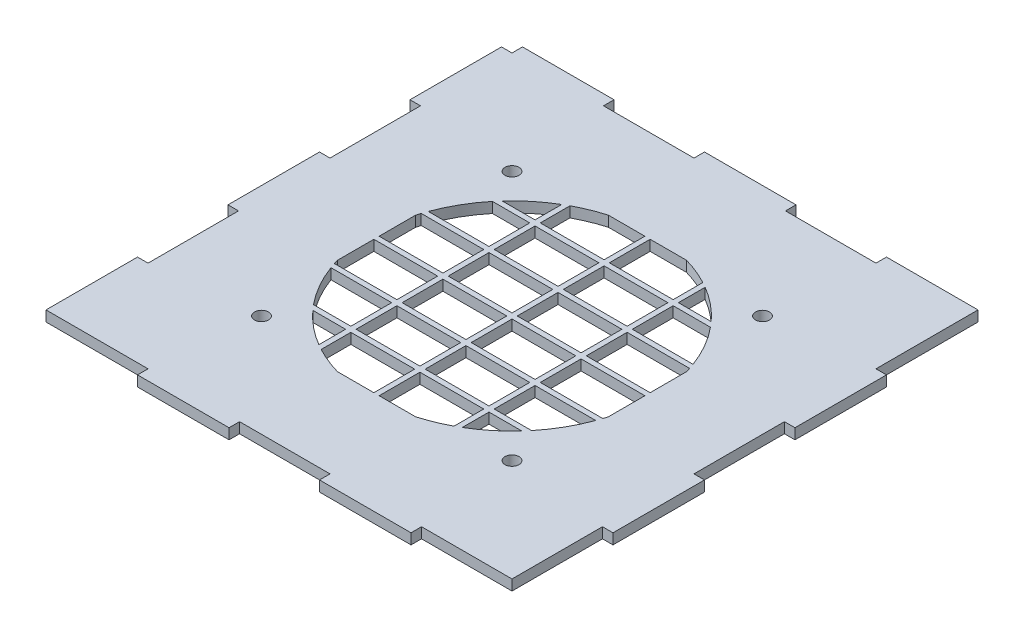
SolidWorks part; units mm, degrees
ref_plane "Front Plane" through (0, 0, 0) normal (0, 0, 1) x (1, 0, 0)
ref_plane "Top Plane" through (0, 0, 0) normal (0, 1, 0) x (1, 0, 0)
ref_plane "Right Plane" through (0, 0, 0) normal (1, 0, 0) x (0, 0, -1)
sketch "Sketch1" plane through (0, 0, 0) normal (0, 1, 0) x (1, 0, 0)
  line L0 (0, 38.675) -> (0, 65) construction
  line L1 (-38.675, 0) -> (-65, 0) construction
  line L2 (0, -38.675) -> (0, -65) construction
  line L7 (11.1493, -38.675) -> (-11.1493, -38.675)
  line L8 (38.675, -11.1493) -> (38.675, 11.1493)
  line L21 (11.1493, 38.675) -> (-11.1493, 38.675)
  line L45 (-38.675, -11.1493) -> (-38.675, 11.1493)
  line L46 (38.675, -38.675) -> (-38.675, 38.675) construction
  line L99 (38.675, 38.675) -> (-38.675, -38.675) construction
  line L116 (65, 38.88) -> (68, 38.88)
  line L117 (-65, -38.88) -> (-65, -13.06)
  line L118 (68, 38.88) -> (68, 12.76)
  line L119 (68, 12.76) -> (65, 12.76)
  line L120 (38.675, 0) -> (65, 0) construction
  line L121 (-13.06, 65) -> (-38.88, 65)
  line L122 (-38.88, 65) -> (-38.88, 68)
  line L123 (-13.06, 65) -> (-13.06, 68)
  line L124 (-13.06, 68) -> (13.06, 68)
  line L125 (13.06, 65) -> (13.06, 68)
  line L126 (38.88, 65) -> (38.88, 68)
  line L127 (38.88, 68) -> (65, 68)
  line L128 (38.88, 65) -> (13.06, 65)
  line L129 (-65, 66.5) -> (-39.18, 66.5) construction
  line L130 (-39.18, 66.5) -> (-38.88, 66.5) construction
  line L131 (-65, 38.88) -> (-68, 38.88)
  line L132 (-65, 13.06) -> (-68, 13.06)
  line L133 (-65, -13.06) -> (-68, -13.06)
  line L134 (-68, 13.06) -> (-68, -13.06)
  line L135 (-65, -38.88) -> (-68, -38.88)
  line L136 (-68, -65) -> (-68, -38.88)
  line L137 (-65, 13.06) -> (-65, 38.88)
  line L138 (-38.88, -65) -> (-64.7, -65)
  line L139 (65, 12.76) -> (65, -13.06)
  line L140 (65, -13.06) -> (68, -13.06)
  line L141 (68, -13.06) -> (68, -39.18)
  line L142 (68, -39.18) -> (65, -39.18)
  line L143 (65, -39.18) -> (65, -65)
  line L144 (65, -65) -> (39.18, -65)
  line L145 (39.18, -65) -> (39.18, -68)
  line L146 (39.18, -68) -> (13.06, -68)
  line L147 (13.06, -68) -> (13.06, -65)
  line L148 (13.06, -65) -> (-12.76, -65)
  line L149 (-12.76, -65) -> (-12.76, -68)
  line L150 (-12.76, -68) -> (-38.88, -68)
  line L151 (-38.88, -68) -> (-38.88, -65)
  line L152 (-64.7, -65) -> (-68, -65)
  line L153 (65, 68) -> (65, 64.7)
  line L154 (65, 64.7) -> (65, 38.88)
  line L155 (-38.88, 68) -> (-65, 68)
  line L156 (-65, 68) -> (-65, 65)
  line L157 (-65, 65) -> (-68, 65)
  line L158 (-68, 65) -> (-68, 38.88)
  arc A9 (-38.675, -11.1493) -> (-11.1493, -38.675) centre (0, 0) ccw
  arc A10 (-11.1493, 38.675) -> (-38.675, 11.1493) centre (0, 0) ccw
  arc A11 (38.675, 11.1493) -> (11.1493, 38.675) centre (0, 0) ccw
  arc A12 (11.1493, -38.675) -> (38.675, -11.1493) centre (0, 0) ccw
  dimension "D3" = 0.3
  dimension "D2" = 80.5
  dimension "D1" = 77.35
  dimension "D4" = 3
  dimension "D5" = 130
extrude "Boss-Extrude1" add sketch "Sketch1" along normal blind 3
sketch "Sketch2" plane through (0, 3, 0) normal (0, 1, 0) x (1, 0, 0)
  line L1 (-65, 40.175) -> (65, 40.175)
  line L2 (-65, 40.175) -> (-65, 38.675)
  line L3 (-65, 38.675) -> (65, 38.675)
  line L4 (65, 40.175) -> (65, 38.675)
  line L5 (-11.1493, -38.675) -> (11.1493, -38.675) construction
  line L7 (-65, 27.0333) -> (-65, 25.5333)
  line L8 (-65, 27.0333) -> (65, 27.0333)
  line L9 (65, 27.0333) -> (65, 25.5333)
  line L10 (-65, 25.5333) -> (65, 25.5333)
  line L11 (-65, 13.8917) -> (-65, 12.3917)
  line L12 (-65, 13.8917) -> (65, 13.8917)
  line L13 (65, 13.8917) -> (65, 12.3917)
  line L14 (-65, 12.3917) -> (65, 12.3917)
  line L15 (-65, 0.75) -> (-65, -0.75)
  line L16 (-65, 0.75) -> (65, 0.75)
  line L17 (65, 0.75) -> (65, -0.75)
  line L18 (-65, -0.75) -> (65, -0.75)
  line L19 (-65, -12.3917) -> (-65, -13.8917)
  line L20 (-65, -12.3917) -> (65, -12.3917)
  line L21 (65, -12.3917) -> (65, -13.8917)
  line L22 (-65, -13.8917) -> (65, -13.8917)
  line L23 (-65, -25.5333) -> (-65, -27.0333)
  line L24 (-65, -25.5333) -> (65, -25.5333)
  line L25 (65, -25.5333) -> (65, -27.0333)
  line L26 (-65, -27.0333) -> (65, -27.0333)
  line L27 (-65, -38.675) -> (-65, -40.175)
  line L28 (-65, -38.675) -> (65, -38.675)
  line L29 (65, -38.675) -> (65, -40.175)
  line L30 (-65, -40.175) -> (65, -40.175)
  line L57 (11.1493, 38.675) -> (-11.1493, 38.675) construction
  line L60 (-65, 38.88) -> (-65, 13.06) construction
  line L61 (65, 38.88) -> (65, 68) construction
  dimension "D1" = 1.5
  dimension "D2" = 7
extrude "Boss-Extrude2" add sketch "Sketch2" against normal through all
sketch "Sketch3" plane through (0, 3, 0) normal (0, 1, 0) x (1, 0, 0)
  line L1 (38.675, 0.75) -> (38.675, 11.1493) construction
  line L2 (-38.675, -38.675) -> (-40.175, -38.675)
  line L3 (-38.675, -38.675) -> (-38.675, 38.675)
  line L4 (-38.675, 38.675) -> (-40.175, 38.675)
  line L5 (-40.175, -38.675) -> (-40.175, 38.675)
  line L6 (-38.675, -0.75) -> (-38.675, -11.1493) construction
  line L8 (-18.9625, -38.675) -> (-18.9625, 38.675)
  line L9 (-18.9625, -38.675) -> (-20.4625, -38.675)
  line L10 (-20.4625, -38.675) -> (-20.4625, 38.675)
  line L11 (-18.9625, 38.675) -> (-20.4625, 38.675)
  line L12 (0.75, -38.675) -> (0.75, 38.675)
  line L13 (0.75, -38.675) -> (-0.75, -38.675)
  line L14 (-0.75, -38.675) -> (-0.75, 38.675)
  line L15 (0.75, 38.675) -> (-0.75, 38.675)
  line L16 (20.4625, -38.675) -> (20.4625, 38.675)
  line L17 (20.4625, -38.675) -> (18.9625, -38.675)
  line L18 (18.9625, -38.675) -> (18.9625, 38.675)
  line L19 (20.4625, 38.675) -> (18.9625, 38.675)
  line L20 (40.175, -38.675) -> (40.175, 38.675)
  line L21 (40.175, -38.675) -> (38.675, -38.675)
  line L22 (38.675, -38.675) -> (38.675, 38.675)
  line L23 (40.175, 38.675) -> (38.675, 38.675)
  line L80 (11.1493, 38.675) -> (-11.1493, 38.675) construction
  line L81 (-11.1493, -38.675) -> (11.1493, -38.675) construction
  dimension "D2" = 1.5
  dimension "D1" = 5
extrude "Boss-Extrude3" add sketch "Sketch3" against normal through all contours L16 L19 L18 L17 | L20 L23 L22 L21 | L14 L15 L12 L13 | L10 L11 L8 L9 | L3 L4 L5 L2 region at (19.7125, 3, 0)
sketch "Sketch4" plane through (0, 3, 0) normal (0, 1, 0) x (1, 0, 0)
  line L5 (-35.75, -35.75) -> (35.75, -35.75) construction
  line L6 (-35.75, -35.75) -> (-35.75, 35.75) construction
  line L7 (-35.75, 35.75) -> (35.75, 35.75) construction
  line L8 (35.75, -35.75) -> (35.75, 35.75) construction
  line L11 (65, 65) -> (-65, 65) construction
  line L12 (65, 38.88) -> (65, 68) construction
  circle A2 centre (-35.75, 35.75) radius 2
  circle A3 centre (35.75, 35.75) radius 2
  circle A4 centre (35.75, -35.75) radius 2
  circle A5 centre (-35.75, -35.75) radius 2
  point P2 (-35.75, 0)
  point P8 (0, 35.75)
  point P23 (0, 65)
  dimension "D2" = 4
  dimension "D1" = 71.5
extrude "Cut-Extrude1" cut sketch "Sketch4" against normal through all
